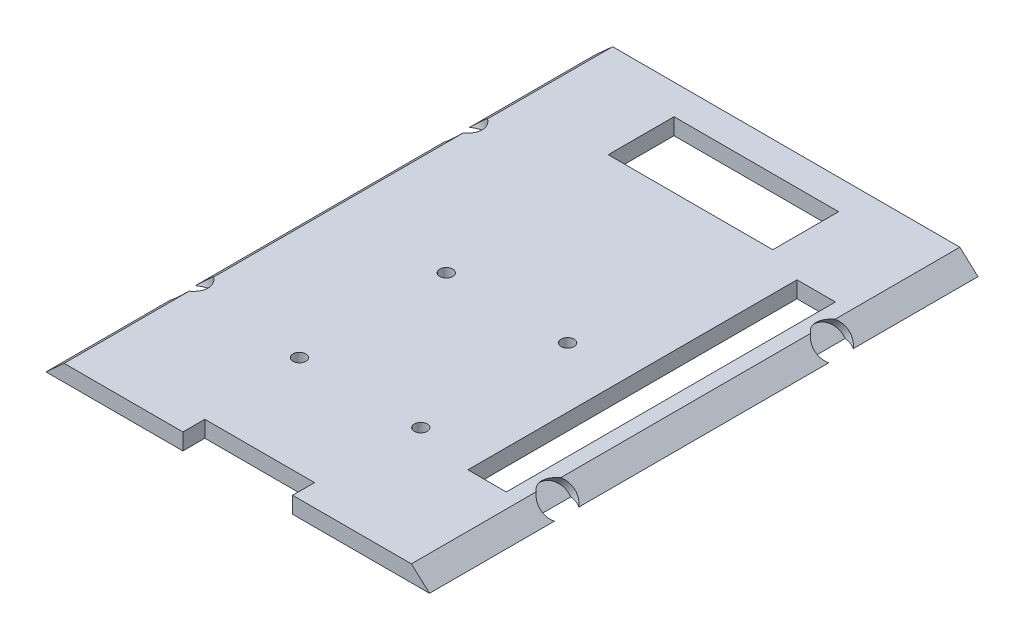
SolidWorks part; units mm, degrees
ref_plane "Front Plane" through (0, 0, 0) normal (0, 0, 1) x (1, 0, 0)
ref_plane "Top Plane" through (0, 0, 0) normal (0, 1, 0) x (1, 0, 0)
ref_plane "Right Plane" through (0, 0, 0) normal (1, 0, 0) x (0, 0, -1)
sketch "Sketch1" plane through (0, 0, 0) normal (0, 0, 1) x (1, 0, 0)
  line L0 (0, 0) -> (0, 44.45) construction
  line L1 (-40.2039, 5.9378) -> (40.2039, 5.9378)
  line L2 (-44.399, 2.1278) -> (44.399, 2.1278)
  line L3 (-40.2039, 5.9378) -> (-44.399, 2.1278)
  line L4 (40.2039, 5.9378) -> (44.399, 2.1278)
  arc A0 (44.399, 2.1278) -> (-44.399, 2.1278) centre (0, 0) ccw construction
  arc A1 (40.2039, 5.9378) -> (-40.2039, 5.9378) centre (0, 0) ccw construction
  dimension "D1" = 88.9
  dimension "D2" = 3.81
  dimension "D3" = 3.81
extrude "Boss-Extrude1" add sketch "Sketch1" along normal blind 127
sketch "Sketch3" plane through (0, 2.1278, 0) normal (0, -1, 0) x (1, 0, 0)
  line L0 (0, 127) -> (0, 0) construction
  line L1 (-44.399, 127) -> (44.399, 127) construction
  line L2 (-44.399, 0) -> (44.399, 0) construction
  line L3 (0, 63.5) -> (44.399, 63.5) construction
  line L4 (-12.7, 127) -> (12.7, 127)
  line L5 (-12.7, 127) -> (-12.7, 121.92)
  line L6 (-12.7, 121.92) -> (12.7, 121.92)
  line L7 (12.7, 127) -> (12.7, 121.92)
  line L8 (44.399, 127) -> (44.399, 0) construction
  line L9 (0, 63.5) -> (-44.399, 63.5) construction
  line L10 (-44.399, 127) -> (-44.399, 0) construction
  line L11 (12.7, -5.08) -> (12.7, 0) construction
  line L13 (-12.7, 0) -> (12.7, 0) construction
  line L14 (-12.7, -5.08) -> (-12.7, 0) construction
  line L15 (-12.7, -5.08) -> (12.7, -5.08) construction
  point P10 (12.7, 124.46)
  dimension "D1" = 25.4
  dimension "D2" = 12.7
  dimension "D3" = 5.08
extrude "Cut-Extrude1" cut sketch "Sketch3" against normal through all
sketch "Sketch5" plane through (0, 2.1278, 0) normal (0, -1, 0) x (1, 0, 0)
  line L0 (12.7, 127) -> (44.399, 127) construction
  line L1 (27.889, 101.6) -> (36.779, 101.6)
  line L2 (27.889, 101.6) -> (27.889, 25.4)
  line L3 (27.889, 25.4) -> (36.779, 25.4)
  line L4 (36.779, 101.6) -> (36.779, 25.4)
  line L5 (44.399, 127) -> (44.399, 0) construction
  dimension "D1" = 76.2
  dimension "D2" = 25.4
  dimension "D3" = 7.62
  dimension "D4" = 8.89
extrude "Cut-Extrude3" cut sketch "Sketch5" against normal through all
sketch "Sketch6" plane through (0, 2.1278, 0) normal (0, -1, 0) x (1, 0, 0)
  line L0 (0, 22.173) -> (0, 6.933) construction
  line L1 (-19.05, 22.173) -> (19.05, 22.173)
  line L2 (-19.05, 22.173) -> (-19.05, 6.933)
  line L3 (-19.05, 6.933) -> (19.05, 6.933)
  line L4 (19.05, 22.173) -> (19.05, 6.933)
  line L5 (0, 121.92) -> (0, 0) construction
  line L6 (-12.7, 121.92) -> (12.7, 121.92) construction
  line L7 (-44.399, 0) -> (44.399, 0) construction
  dimension "D1" = 38.1
  dimension "D2" = 15.24
  dimension "D3" = 0
extrude "Cut-Extrude4" cut sketch "Sketch6" against normal through all
sketch "Sketch7" plane through (21.1272, 23.263, 0) normal (0.6723, 0.7403, 0) x (0.7403, -0.6723, 0)
  line L0 (28.6033, -127) -> (28.6033, -0.0263) construction
  line L1 (31.4368, -127) -> (25.7698, -127) construction
  line L2 (25.7698, -63.5) -> (31.4368, -63.5) construction
  line L3 (25.7698, -127) -> (25.7698, 0) construction
  line L4 (31.4368, -127) -> (31.4368, 0) construction
  circle A0 centre (28.6033, -95.2631) radius 4.0005
  circle A1 centre (28.6033, -31.7369) radius 4.0005
  point P6 (28.6033, -63.5131)
  dimension "D1" = 8.001
  dimension "D2" = 31.75
extrude "Cut-Extrude5" cut sketch "Sketch7" against normal blind 2
sketch "Sketch8" plane through (-21.1272, 23.263, 0) normal (-0.6723, 0.7403, 0) x (0.7403, 0.6723, 0)
  line L0 (-28.6033, 0) -> (-28.6033, -127.0519) construction
  line L1 (-25.7698, 0) -> (-31.4368, 0) construction
  line L2 (-25.7698, -63.5) -> (-31.4368, -63.5) construction
  line L3 (-25.7698, -127) -> (-25.7698, 0) construction
  line L4 (-31.4368, -127) -> (-31.4368, 0) construction
  circle A0 centre (-28.6033, -31.776) radius 4.0005
  circle A1 centre (-28.6033, -95.224) radius 4.0005
  point P12 (-28.6033, -63.526)
  dimension "D1" = 8.001
  dimension "D2" = 31.75
extrude "Cut-Extrude6" cut sketch "Sketch8" against normal blind 2
sketch "Sketch9" plane through (0, 5.9378, 0) normal (0, 1, 0) x (1, 0, 0)
  line L0 (-0.0719, -127) -> (-0.0719, 0) construction
  line L1 (-0.0719, -103.6016) -> (-0.0719, -59.6016) construction
  line L2 (18.9781, -103.6016) -> (-19.1219, -103.6016) construction
  line L3 (40.2039, 0) -> (-40.2039, 0) construction
  line L4 (18.9781, -103.6016) -> (18.9781, -59.6016) construction
  line L5 (40.2039, -63.5) -> (-40.2039, -63.5) construction
  line L6 (18.9781, -59.6016) -> (-19.1219, -59.6016) construction
  line L7 (40.2039, -92.4391) -> (40.2039, -34.5609) construction
  line L8 (-40.2039, -92.4) -> (-40.2039, -34.6) construction
  line L9 (-19.1219, -103.6016) -> (-19.1219, -59.6016) construction
  line L11 (-40.2039, -127) -> (-40.2039, -98.0481) construction
  line L12 (18.9781, -81.6016) -> (-19.1219, -81.6016) construction
  circle A0 centre (13.9781, -98.6016) radius 1.5
  circle A1 centre (-14.1219, -98.6016) radius 1.5
  circle A2 centre (-14.1219, -64.6016) radius 1.5
  circle A3 centre (13.9781, -64.6016) radius 1.5
  dimension "D8" = 3
  dimension "D1" = 127
  dimension "D2" = 44
  dimension "D3" = 38.1
  dimension "D4" = 0
  dimension "D5" = 40.132
  dimension "D6" = 5
  dimension "D7" = 5
extrude "Cut-Extrude8" cut sketch "Sketch9" against normal through all
